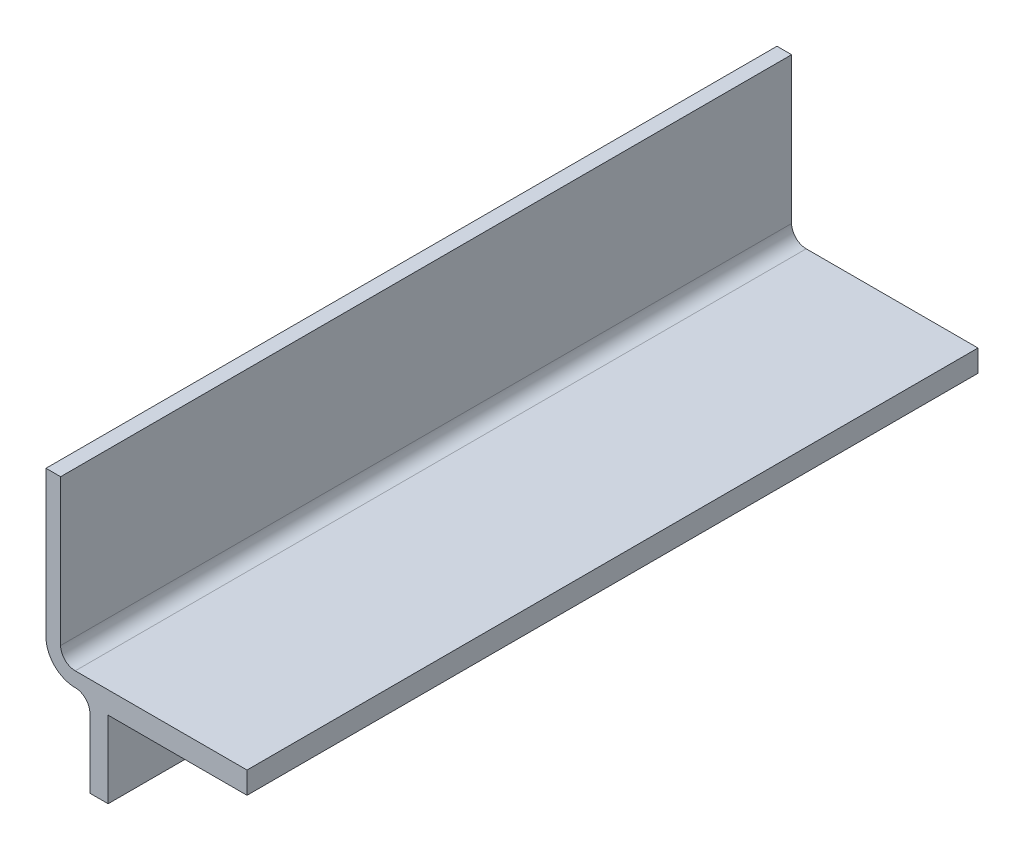
SolidWorks part; units mm, degrees
ref_plane "Piano frontale" through (0, 0, 0) normal (0, 0, 1) x (1, 0, 0)
ref_plane "Piano superiore" through (0, 0, 0) normal (0, 1, 0) x (1, 0, 0)
ref_plane "Piano destro" through (0, 0, 0) normal (1, 0, 0) x (0, 0, -1)
sketch "Schizzo1" plane through (0, 0, 0) normal (0, 0, 1) x (1, 0, 0)
  line L0 (0, 0) -> (-2.5, 0)
  line L1 (-2.5, 0) -> (-2.5, 11.5)
  line L2 (-2.5, 11.5) -> (-8.5, 11.5)
  line L3 (-8.5, 11.5) -> (-8.5, 35.5)
  line L4 (-8.5, 35.5) -> (-6.5, 35.5)
  line L5 (-6.5, 35.5) -> (-6.5, 13.5)
  line L6 (-6.5, 13.5) -> (19, 13.5)
  line L7 (19, 13.5) -> (19, 10.5)
  line L8 (19, 10.5) -> (0, 10.5)
  line L9 (0, 10.5) -> (0, 0)
  dimension "D1" = 3
  dimension "D2" = 19
  dimension "D3" = 2
  dimension "D4" = 2
  dimension "D5" = 6
  dimension "D6" = 2.5
  dimension "D7" = 10.5
  dimension "D8" = 24
extrude "Estrusione-Estrusione1" add sketch "Schizzo1" along normal blind 100
fillet "Raccordo1" radius 2 2 edges at (-2.5, 11.5, 50) (-6.5, 13.5, 50)
fillet "Raccordo2" radius 4 1 edges at (-8.5, 11.5, 50)
sketch "Schizzo2" plane through (-2.5, 0, 0) normal (-1, 0, 0) x (0, 0, 1)
  line L0 (100, 0) -> (0, 0) construction
  line L1 (100, 9.5) -> (100, 0) construction
  line L2 (15, 4.5) -> (85, 4.5) construction
  line L4 (0, 9.5) -> (0, 0) construction
  point P0 (85, 4.5)
  point P2 (15, 4.5)
  dimension "D1" = 4.5
  dimension "D2" = 15
  dimension "D3" = 15
hole_wizard "Foro svasato per Vite M4-1" positions "Schizzo2" profile "Schizzo4" countersink size "M4" standard "ISO"
sketch "Schizzo4" plane through (-2.5, 4.5, 85) normal (0, 1, 0) x (0, 0, 1)
  line L0 (0, 0) -> (0, 189.3519)
  line L1 (0, 189.3519) -> (2.25, 188)
  line L2 (2.25, 188) -> (2.25, 2.45)
  line L3 (2.25, 2.45) -> (4.7, 0)
  line L5 (4.7, 0) -> (0, 0)
  line L6 (-2.25, 2.45) -> (-4.7, 0) construction
  line L10 (0, 189.3519) -> (-2.25, 188) construction
  line L11 (0, -6.35) -> (0, 107.95) construction
  dimension "Hole Dia." = 4.5
  dimension "Hole Depth" = 188
  dimension "Near C'Sink Dia." = 9.4
  dimension "Near C'Sink Angle" = 90
  dimension "Drill Angle" = 118
